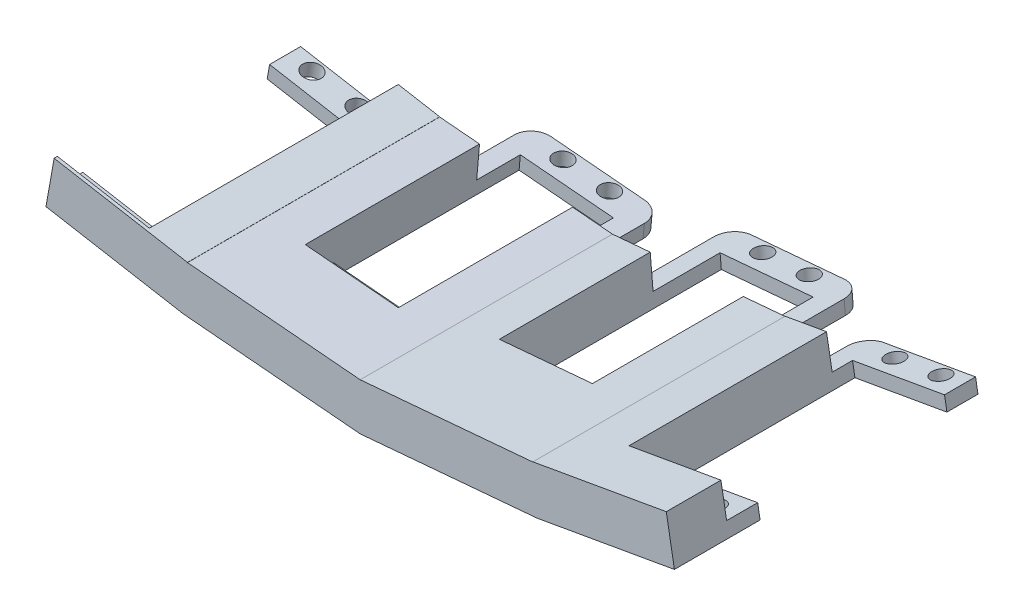
SolidWorks part; units mm, degrees
note: The reader was unsure of these and kept them because the rebuilt part matched: shared geometry of "Sketch14<3>", "Sketch16<3>", "Sketch18<3>", "Sketch17<3>", "Sketch16<4>", "Sketch17<4>", "Sketch18<4>".
ref_plane "Front Plane" through (0, 0, 0) normal (0, 0, 1) x (1, 0, 0)
ref_plane "Top Plane" through (0, 0, 0) normal (0, 1, 0) x (1, 0, 0)
ref_plane "Right Plane" through (0, 0, 0) normal (1, 0, 0) x (0, 0, -1)
sketch "Sketch9" plane through (0, 0, 0) normal (0, 1, 0) x (1, 0, 0)
  line L0 (0, 0) -> (0, 44.7413)
ref_plane "Ring Plane" through (0, 0, 0) normal (0.0872, 0.9962, 0) x (0, 0, -1)
ref_plane "Middle Plane" through (0, 0, 0) normal (-0.0872, 0.9962, 0) x (0, 0, -1)
sketch "Sketch10" plane through (0, 0, 0) normal (0.0872, 0.9962, 0) x (0, 0, -1)
  line L1 (0, 0) -> (70, 0)
  line L2 (0, 0) -> (0, 38)
  line L3 (0, 38) -> (70, 38)
  line L4 (70, 0) -> (70, 38)
  dimension "D1" = 38
  dimension "D2" = 70
extrude "Boss-Extrude6" add sketch "Sketch10" along normal blind 10
sketch "Sketch11" plane through (0, 0, 0) normal (-0.0872, 0.9962, 0) x (0, 0, -1)
  line L1 (0, 0) -> (75, 0)
  line L2 (0, 0) -> (0, -38)
  line L3 (0, -38) -> (75, -38)
  line L4 (75, 0) -> (75, -38)
  dimension "D1" = 38
  dimension "D2" = 75
extrude "Boss-Extrude7" add sketch "Sketch11" along normal blind 10
ref_plane "Pinky Plane" through (-0.5751, -3.2616, 0) normal (0.1736, 0.9848, 0) x (0, 0, 1)
sketch "Sketch12" plane through (-0.5751, -3.2616, 0) normal (0.1736, 0.9848, 0) x (0, 0, 1)
  line L1 (0, -38.727) -> (-54, -38.727)
  line L2 (0, -38.727) -> (0, -67.727)
  line L3 (0, -67.727) -> (-54, -67.727)
  line L4 (-54, -38.727) -> (-54, -67.727)
  dimension "D1" = 29
  dimension "D2" = 54
extrude "Boss-Extrude8" add sketch "Sketch12" along normal blind 10 separate body contours L1 L4 L3 L2
ref_plane "Pointer Plane" through (0.5751, -3.2616, 0) normal (-0.1736, 0.9848, 0) x (0, 0, -1)
sketch "Sketch13" plane through (0.5751, -3.2616, 0) normal (-0.1736, 0.9848, 0) x (0, 0, -1)
  line L1 (0, -38.727) -> (65, -38.727)
  line L2 (0, -38.727) -> (0, -67.727)
  line L3 (0, -67.727) -> (65, -67.727)
  line L4 (65, -38.727) -> (65, -67.727)
  dimension "D1" = 29
  dimension "D2" = 65
extrude "Boss-Extrude9" add sketch "Sketch13" along normal blind 10 separate body contours L4 L1 L2 L3
sketch "Sketch14" plane through (1.1614, 6.5865, 0) normal (0.1736, 0.9848, 0) x (0.9848, -0.1736, 0)
  line L0 (-57.727, 54) -> (-57.727, 40.7822)
  line L1 (-67.727, 54) -> (-62.727, 54)
  line L2 (-67.727, 54) -> (-67.727, 51.5)
  line L3 (-67.727, 51.5) -> (-62.727, 51.5)
  line L4 (-62.727, 54) -> (-62.727, 51.5)
  line L5 (-67.727, 7.35) -> (-47.727, 7.35)
  line L6 (-67.727, 27.35) -> (-56.2193, 27.35)
  line L7 (-67.727, 27.35) -> (-47.727, 27.35)
  line L8 (-67.727, 27.35) -> (-67.727, 47.35)
  line L9 (-67.727, 54) -> (-47.727, 54)
  line L10 (-67.727, 54) -> (-67.727, 0.7)
  line L11 (-67.727, 0.7) -> (-47.727, 0.7)
  line L12 (-47.727, 54) -> (-47.727, 0.7)
  line L13 (-67.727, 47.35) -> (-47.727, 47.35)
  line L14 (-47.727, 27.35) -> (-47.727, 47.35)
  circle A0 centre (-62.727, 51.5) radius 2
  circle A1 centre (-52.727, 51.5) radius 2
  circle A2 centre (-52.727, 3.2) radius 2
  circle A3 centre (-62.727, 3.2) radius 2
  line M15 (-38.727, 54) -> (-67.727, 54)
  line M16 (-67.727, 54) -> (-67.727, 0)
  dimension "D3" = 4
  dimension "D2" = 2.5
  dimension "D4" = 53.3
  dimension "D5" = 20
  dimension "D6" = 20
extrude "Pinky Hole Extrude" cut sketch "Sketch14" against normal up to next (10 mm away)
extrude "Cut-Extrude12" cut sketch "Sketch14<3>" against normal blind 7 contours A0 L3 L13 L0 L4 M16 M15 | A0 L4 L3 M15 M16 | L0 L13 L12 A1 M15 | L12 L5 L11 A2 A3 M16
sketch "Sketch14<3>" plane through (1.1614, 6.5865, 0) normal (0.1736, 0.9848, 0) x (0.9848, -0.1736, 0) same geometry as "Sketch14"
sketch "Sketch16" plane through (0.8716, 9.9619, 0) normal (0.0872, 0.9962, 0) x (0.9962, -0.0872, 0)
  line L0 (-0.8749, 70) -> (-38, 70) construction
  line L1 (-9.4374, 70) -> (-29.4374, 70)
  line L2 (-19.4374, 70) -> (-19.4374, 16.7)
  line L3 (-9.4374, 16.7) -> (-29.4374, 16.7)
  line L4 (-29.4374, 70) -> (-29.4374, 16.7)
  line L5 (-29.4374, 43.35) -> (-22.8425, 43.35)
  line L6 (-29.4374, 70) -> (-24.4374, 70)
  line L7 (-29.4374, 70) -> (-29.4374, 67.5)
  line L8 (-29.4374, 67.5) -> (-24.4374, 67.5)
  line L9 (-24.4374, 70) -> (-24.4374, 67.5)
  line L10 (-14.4374, 70) -> (-14.4374, 67.5)
  line L11 (-9.4374, 67.5) -> (-14.4374, 67.5)
  line L12 (-9.4374, 70) -> (-9.4374, 67.5)
  line L13 (-9.4374, 70) -> (-14.4374, 70)
  line L14 (-9.4374, 43.35) -> (-16.0323, 43.35)
  line L15 (-9.4374, 70) -> (-9.4374, 16.7)
  line L16 (-0.8749, 54) -> (-9.4374, 54)
  line L17 (-38, 70) -> (-29.4374, 70)
  line L18 (-38, 70) -> (-38, 54)
  line L19 (-38, 54) -> (-29.4374, 54)
  line L20 (-29.4374, 70) -> (-29.4374, 54)
  line L21 (-9.4374, 70) -> (-9.4374, 54)
  line L22 (-0.8749, 70) -> (-9.4374, 70)
  line L23 (-0.8749, 70) -> (-0.8749, 54)
  line L24 (-29.4374, 23.35) -> (-9.4374, 23.35)
  line L25 (-29.4374, 43.35) -> (-9.4374, 43.35)
  line L26 (-29.4374, 43.35) -> (-29.4374, 63.35)
  line L27 (-29.4374, 63.35) -> (-9.4374, 63.35)
  line L28 (-9.4374, 43.35) -> (-9.4374, 63.35)
  circle A0 centre (-24.4374, 67.5) radius 2
  circle A1 centre (-24.4374, 19.2) radius 2
  circle A2 centre (-14.4374, 19.2) radius 2
  circle A3 centre (-14.4374, 67.5) radius 2
  line M11 (-0.8749, 0) -> (-0.8749, 70)
  line M12 (-0.8749, 70) -> (-38, 70)
  line M13 (-38, 70) -> (-38, 0)
  dimension "D5" = 4
  dimension "D1" = 53.3
  dimension "D2" = 10
  dimension "D3" = 2.5
  dimension "D6" = 16
  dimension "D7" = 20
extrude "Ring Hole Extrude" cut sketch "Sketch16" against normal blind 7 contours A0 L8 L4 L27 L2 L1 L9 | A0 L9 L4 L8 M12 | L11 A3 L10 L1 L2 L27 L15 | L10 A3 L11 L12 M12 | L24 L2 L3 L15 A2 | L24 L4 L3 L2 A1
extrude "Cut-Extrude14" cut sketch "Sketch16<3>" against normal up to next (10 mm away) contours L8 A0 L9 | L9 A0 L8 | A3 L10 L11 | A3 L11 L10 | A1 | A2 | L25 L2 L24 L15 L14 | L25 L5 L4 L24 L2 | L27 L2 L25 L14 L15 L21 | L27 L20 L4 L5 L25 L2
sketch "Sketch16<3>" plane through (0.8716, 9.9619, 0) normal (0.0872, 0.9962, 0) x (0.9962, -0.0872, 0) same geometry as "Sketch16"
sketch "Sketch17" plane through (-0.8716, 9.9619, 0) normal (-0.0872, 0.9962, 0) x (0.9962, 0.0872, 0)
  line L0 (29, 75) -> (9, 75)
  line L1 (19, 75) -> (19, 21.7)
  line L2 (29, 21.7) -> (9, 21.7)
  line L3 (9, 75) -> (9, 21.7)
  line L4 (9, 48.35) -> (15.5949, 48.35)
  line L5 (9, 75) -> (14, 75)
  line L6 (9, 75) -> (9, 72.5)
  line L7 (9, 72.5) -> (14, 72.5)
  line L8 (14, 75) -> (14, 72.5)
  line L9 (24, 75) -> (24, 72.5)
  line L10 (29, 72.5) -> (24, 72.5)
  line L11 (29, 75) -> (29, 72.5)
  line L12 (29, 75) -> (24, 75)
  line L13 (29, 48.35) -> (22.4051, 48.35)
  line L14 (29, 75) -> (29, 21.7)
  line L15 (38, 75) -> (0, 75) construction
  line L16 (38, 54) -> (29, 54)
  line L17 (0, 75) -> (9, 75)
  line L18 (0, 75) -> (0, 54)
  line L19 (0, 54) -> (9, 54)
  line L20 (9, 75) -> (9, 54)
  line L21 (29, 75) -> (29, 54)
  line L22 (38, 75) -> (29, 75)
  line L23 (38, 75) -> (38, 54)
  line L24 (9, 28.35) -> (29, 28.35)
  line L25 (9, 48.35) -> (29, 48.35)
  line L26 (9, 48.35) -> (9, 68.35)
  line L27 (9, 68.35) -> (29, 68.35)
  line L28 (29, 48.35) -> (29, 68.35)
  circle A0 centre (14, 72.5) radius 2
  circle A1 centre (14, 24.2) radius 2
  circle A2 centre (24, 24.2) radius 2
  circle A3 centre (24, 72.5) radius 2
  point P25 (19, 75)
  line M6 (0, 70) -> (0.8749, 70)
  line M7 (0.8749, 70) -> (0.8749, 0)
  line M9 (38, 0) -> (38, 75)
  line M10 (38, 75) -> (0, 75)
  line M11 (0, 75) -> (0, 70)
  dimension "D5" = 4
  dimension "D1" = 53.3
  dimension "D2" = 10
  dimension "D3" = 2.5
  dimension "D7" = 20
  dimension "D6" = 21
sketch "Sketch18" plane through (-1.1614, 6.5865, 0) normal (-0.1736, 0.9848, 0) x (0.9848, 0.1736, 0)
  line L0 (67.727, 65) -> (47.727, 65)
  line L1 (57.727, 65) -> (57.727, 11.7)
  line L2 (67.727, 11.7) -> (47.727, 11.7)
  line L3 (47.727, 65) -> (47.727, 11.7)
  line L4 (47.727, 38.35) -> (54.3219, 38.35)
  line L5 (47.727, 65) -> (52.727, 65)
  line L6 (47.727, 65) -> (47.727, 62.5)
  line L7 (47.727, 62.5) -> (52.727, 62.5)
  line L8 (52.727, 65) -> (52.727, 62.5)
  line L9 (62.727, 65) -> (62.727, 62.5)
  line L10 (67.727, 62.5) -> (62.727, 62.5)
  line L11 (67.727, 65) -> (67.727, 62.5)
  line L12 (67.727, 65) -> (62.727, 65)
  line L13 (67.727, 38.35) -> (61.1321, 38.35)
  line L14 (67.727, 65) -> (67.727, 11.7)
  line L15 (67.727, 0) -> (67.727, 65) construction
  line L16 (47.727, 18.35) -> (67.727, 18.35)
  line L17 (38.727, 65) -> (47.727, 65)
  line L18 (38.727, 65) -> (38.727, 54)
  line L19 (38.727, 54) -> (47.727, 54)
  line L20 (47.727, 65) -> (47.727, 54)
  line L21 (47.727, 38.35) -> (67.727, 38.35)
  line L22 (47.727, 38.35) -> (47.727, 58.35)
  line L23 (47.727, 58.35) -> (67.727, 58.35)
  line L24 (67.727, 38.35) -> (67.727, 58.35)
  circle A0 centre (52.727, 62.5) radius 2
  circle A1 centre (52.727, 14.2) radius 2
  circle A2 centre (62.727, 14.2) radius 2
  circle A3 centre (62.727, 62.5) radius 2
  line M11 (67.727, 65) -> (38.727, 65)
  line M12 (38.727, 65) -> (38.727, 0)
  line M14 (67.727, 0) -> (67.727, 65)
  dimension "D5" = 4
  dimension "D1" = 53.3
  dimension "D2" = 10
  dimension "D3" = 2.5
  dimension "D7" = 20
  dimension "D6" = 11
extrude "Cut-Extrude15" cut sketch "Sketch17" against normal up to next (10 mm away) contours L7 A0 L8 | L8 A0 L7 | A3 L9 L10 | A3 L10 L9 | A1 | A2 | L25 L4 L3 L24 L1 | L25 L1 L24 L14 L13 | L27 L1 L25 L13 L14 L21 | L27 L20 L3 L4 L25 L1
extrude "Cut-Extrude16" cut sketch "Sketch18" against normal up to next (10 mm away) contours L7 A0 L8 | L8 A0 L7 | A3 L9 L10 | A3 L10 L9 | A2 | A1 | L23 L1 L21 L13 M14 | L23 L20 L3 L4 L21 L1 | L21 L4 L3 L16 L1 | L21 L1 L16 L14 L13
extrude "Cut-Extrude17" cut sketch "Sketch18<3>" against normal blind 7
sketch "Sketch18<3>" plane through (-1.1614, 6.5865, 0) normal (-0.1736, 0.9848, 0) x (0.9848, 0.1736, 0) same geometry as "Sketch18"
extrude "Cut-Extrude18" cut sketch "Sketch17<3>" against normal blind 7
sketch "Sketch17<3>" plane through (-0.8716, 9.9619, 0) normal (-0.0872, 0.9962, 0) x (0.9962, 0.0872, 0) same geometry as "Sketch17"
extrude "Cut-Extrude19" cut sketch "Sketch16<4>" against normal up to next contours L19 L4 M13 M12 | L16 L12 L15 M11 M12
sketch "Sketch16<4>" plane through (0.8716, 9.9619, 0) normal (0.0872, 0.9962, 0) x (0.9962, -0.0872, 0) same geometry as "Sketch16"
extrude "Cut-Extrude20" cut sketch "Sketch17<4>" against normal up to next contours L19 L3 M7 M10 M11 M6 | L16 L11 L14 M9 M10
sketch "Sketch17<4>" plane through (-0.8716, 9.9619, 0) normal (-0.0872, 0.9962, 0) x (0.9962, 0.0872, 0) same geometry as "Sketch17"
extrude "Cut-Extrude21" cut sketch "Sketch18<4>" against normal up to next contours L19 L3 M12 M11
sketch "Sketch18<4>" plane through (-1.1614, 6.5865, 0) normal (-0.1736, 0.9848, 0) x (0.9848, 0.1736, 0) same geometry as "Sketch18"
sketch "Sketch21" plane through (0, 0, 0) normal (0, 1, 0) x (1, 0, 0)
  line L0 (0, 54) -> (-8.53, 54) construction
  line L1 (-4.265, 54) -> (4.5526, 54)
  line L2 (-4.265, 54) -> (-4.265, 83.3291)
  line L3 (-4.265, 83.3291) -> (4.5526, 83.3291)
  line L4 (4.5526, 54) -> (4.5526, 83.3291)
extrude "Cut-Extrude22" cut sketch "Sketch21" along normal up to next
sketch "Sketch22" plane through (0, 0, -54) normal (0, 0, -1) x (-1, 0, 0)
  line L0 (36.9838, 13.2739) -> (38.7137, 3.4633)
  line L1 (38.4902, 3.4239) -> (-37.34, -9.9471) construction
  line L2 (36.9772, 13.3113) -> (38.7137, 3.4633) construction
  line L3 (38.7137, 3.4633) -> (37.8554, 3.3119)
  line L4 (24.5141, 2.1447) -> (-24.5141, -2.1447) construction
  line L5 (37.8554, 3.3119) -> (36.9838, 13.2739) construction
  line L6 (37.8554, 3.3119) -> (36.9838, 13.2739)
  line L7 (-36.9838, 13.2739) -> (-37.8554, 3.3119)
  line L8 (40.0482, -10.4246) -> (-41.1984, 3.9014) construction
  line L9 (-37.8554, 3.3119) -> (-36.9838, 13.2739) construction
  line L10 (-37.8554, 3.3119) -> (-38.7137, 3.4633)
  line L11 (-38.7137, 3.4633) -> (-36.9838, 13.2739)
  line M1 (37.8554, 3.3119) -> (36.9838, 13.2739)
extrude "Boss-Extrude10" add sketch "Sketch22" against normal blind 54 contours L3 L0 M1 | L11 L10 L7
sketch "Sketch25" plane through (47.0019, 8.2877, 0) normal (-0.9848, -0.1736, 0) x (0, 0, 1)
  line L1 (-65, -0.3119) -> (-58.35, -0.3119)
  line L2 (-65, -0.3119) -> (-65, -3.3119)
  line L3 (-65, -3.3119) -> (-58.35, -3.3119)
  line L4 (-58.35, -0.3119) -> (-58.35, -3.3119)
extrude "Boss-Extrude12" add sketch "Sketch25" along normal blind 4
sketch "Sketch26" plane through (28.8896, 2.5275, 0) normal (0.9962, 0.0872, 0) x (0, 0, -1)
  line L1 (68.35, 3) -> (75, 3)
  line L2 (68.35, 3) -> (68.35, 0)
  line L3 (68.35, 0) -> (75, 0)
  line L4 (75, 3) -> (75, 0)
extrude "Boss-Extrude13" add sketch "Sketch26" along normal blind 4
sketch "Sketch27" plane through (8.9658, 0.7844, 0) normal (-0.9962, -0.0872, 0) x (0, 0, 1)
  line L1 (-75, 3) -> (-68.35, 3)
  line L2 (-75, 3) -> (-75, 0)
  line L3 (-75, 0) -> (-68.35, 0)
  line L4 (-68.35, 3) -> (-68.35, 0)
extrude "Boss-Extrude14" add sketch "Sketch27" along normal blind 4
sketch "Sketch28" plane through (-9.4015, 0.8225, 0) normal (0.9962, -0.0872, 0) x (0, 0, -1)
  line L1 (63.35, 3) -> (70, 3)
  line L2 (63.35, 3) -> (63.35, 0)
  line L3 (63.35, 0) -> (70, 0)
  line L4 (70, 3) -> (70, 0)
extrude "Boss-Extrude15" add sketch "Sketch28" along normal blind 4
sketch "Sketch29" plane through (-29.3254, 2.5656, 0) normal (-0.9962, 0.0872, 0) x (0, 0, 1)
  line L1 (-70, 3) -> (-63.35, 3)
  line L2 (-70, 3) -> (-70, 0)
  line L3 (-70, 0) -> (-63.35, 0)
  line L4 (-63.35, 3) -> (-63.35, 0)
extrude "Boss-Extrude16" add sketch "Sketch29" along normal blind 4
sketch "Sketch30" plane through (0, 0, -58.35) normal (0, 0, 1) x (1, 0, 0)
  line L0 (43.1168, 7.2859) -> (43.6378, 4.3315)
  line L1 (43.1168, 7.2859) -> (47.056, 7.9805)
  line L2 (43.6378, 4.3315) -> (47.577, 5.0261)
  line L3 (47.056, 7.9805) -> (47.577, 5.0261)
extrude "Boss-Extrude17" add sketch "Sketch30" along normal up to next
sketch "Sketch31" plane through (0, 0, -68.35) normal (0, 0, 1) x (1, 0, 0)
  line L0 (4.7195, 3.4244) -> (4.981, 0.4358)
  line L1 (4.7195, 3.4244) -> (8.7043, 3.773)
  line L2 (4.981, 0.4358) -> (8.9658, 0.7844)
  line L3 (8.7043, 3.773) -> (8.9658, 0.7844)
  line L4 (32.613, 5.8647) -> (32.8744, 2.8761)
  line L5 (32.613, 5.8647) -> (28.6282, 5.5161)
  line L6 (32.8744, 2.8761) -> (28.8896, 2.5275)
  line L7 (28.6282, 5.5161) -> (28.8896, 2.5275)
  dimension "D2" = 4
extrude "Boss-Extrude18" add sketch "Sketch31" along normal up to next
sketch "Sketch32" plane through (0, 0, -63.35) normal (0, 0, 1) x (1, 0, 0)
  line L0 (-33.0487, 5.9028) -> (-33.3102, 2.9143)
  line L1 (-33.0487, 5.9028) -> (-29.064, 5.5542)
  line L2 (-33.3102, 2.9143) -> (-29.3254, 2.5656)
  line L3 (-29.064, 5.5542) -> (-29.3254, 2.5656)
  line L4 (-5.1553, 3.4625) -> (-5.4168, 0.4739)
  line L5 (-5.1553, 3.4625) -> (-9.1401, 3.8111)
  line L6 (-5.4168, 0.4739) -> (-9.4015, 0.8225)
  line L7 (-9.1401, 3.8111) -> (-9.4015, 0.8225)
  dimension "D2" = 4
extrude "Boss-Extrude19" add sketch "Sketch32" along normal up to next
fillet "Fillet1" radius 4 5 edges at (-5.286, 1.9682, -70) (-33.1795, 4.4086, -70) (4.8502, 1.9301, -75) (32.7437, 4.3704, -75) (43.3773, 5.8087, -65)
equation "\"Servo Width\"= 20"
equation "\"Servo Height\"= 40"
equation "\"Ring Height\"= 16"
equation "\"Middle Height\"= 21"
equation "\"Pointer Height\"= 11"
equation "\"Finger Gap\"= 18"
equation "\"Servo Total Height\"= 53.3"
equation "\"Servo Screw Height\"= 2.5"
equation "\"Servo Screw Width\"= 5"
equation "\"Servo Screw Diameter\"= 4"
equation "\"D1@Sketch10\"=\"Servo Width\"+\"Finger Gap\""
equation "\"Length\"= 54"
equation "\"D2@Sketch10\"=\"Length\"+\"Ring Height\""
equation "\"Thinkness\"= 10"
equation "\"Take away amount\"= 7"
equation "\"D1@Boss-Extrude6\"=\"Thinkness\""
equation "\"D1@Sketch11\"=\"Servo Width\"+\"Finger Gap\""
equation "\"D2@Sketch11\"=\"Length\"+\"Middle Height\""
equation "\"D1@Boss-Extrude7\"=\"Thinkness\""
equation "\"Curve\"= 5deg"
equation "\"D1@Sketch12\"=\"Servo Width\"+\"Finger Gap\"/2"
equation "\"D2@Sketch12\"=\"Length\""
equation "\"D1@Sketch13\"=\"Servo Width\"+\"Finger Gap\"/2"
equation "\"D2@Sketch13\"=\"Length\"+\"Pointer Height\""
equation "\"D1@Sketch14\"=\"Servo Screw Width\""
equation "\"D2@Sketch14\"=\"Servo Screw Height\""
equation "\"D3@Sketch14\"=\"Servo Screw Diameter\""
equation "\"D1@Sketch16\"=\"Servo Total Height\""
equation "\"D2@Sketch16\"=\"Servo Width\"/2"
equation "\"D3@Sketch16\"=\"Servo Screw Height\""
equation "\"D4@Sketch16\"=\"Servo Screw Width\""
equation "\"D5@Sketch16\"=\"Servo Screw Diameter\""
equation "\"D1@Cut-Extrude17\"=\"Take away amount\""
equation "\"D1@Cut-Extrude18\"=\"Take away amount\""
equation "\"D1@Ring Hole Extrude\" = \"Take away amount\""
equation "\"D6@Sketch16\"=\"Ring Height\""
equation "\"D6@Sketch17\"=\"Middle Height\""
equation "\"D6@Sketch18\"=\"Pointer Height\""
equation "\"D1@Boss-Extrude10\"=\"Length\""
equation "\"Thumb Plane Angle\"= 45deg"
equation "\"Thumb Distance\"= 10"
equation "\"D6@Sketch14\"=\"Servo Height\"/2"
equation "\"D7@Sketch16\"=\"Servo Height\"/2"
equation "\"D7@Sketch17\"=\"Servo Height\"/2"
equation "\"D7@Sketch18\"=\"Servo Height\"/2"
equation "\"Top Screw Plate Distance\"= 4"
equation "\"D1@Boss-Extrude12\"=\"Top Screw Plate Distance\""
equation "\"D1@Boss-Extrude13\"=\"Top Screw Plate Distance\""
equation "\"D1@Boss-Extrude14\"=\"Top Screw Plate Distance\""
equation "\"D1@Boss-Extrude15\"=\"Top Screw Plate Distance\""
equation "\"D1@Boss-Extrude16\"=\"Top Screw Plate Distance\""
equation "\"D1@Sketch30\"=\"Top Screw Plate Distance\""
equation "\"D1@Sketch31\"=\"Top Screw Plate Distance\""
equation "\"D2@Sketch31\"=\"Top Screw Plate Distance\""
equation "\"D1@Sketch32\"=\"Top Screw Plate Distance\""
equation "\"D2@Sketch32\"=\"Top Screw Plate Distance\""
